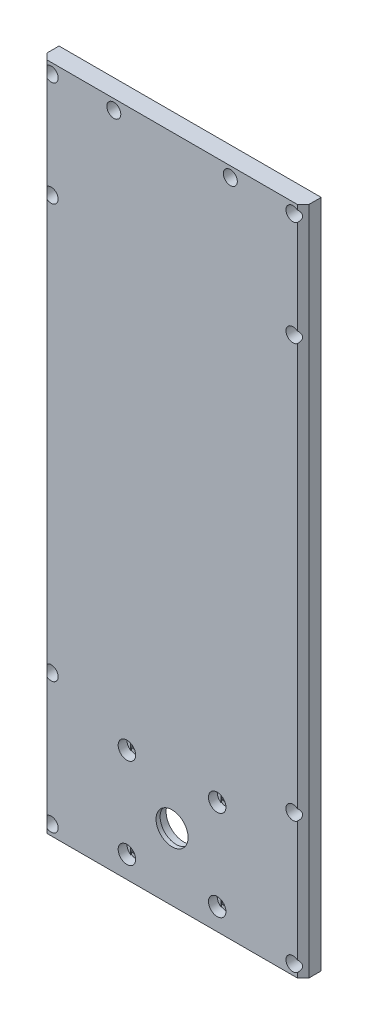
SolidWorks part; units mm, degrees
ref_plane "Front Plane" through (0, 0, 0) normal (0, 0, 1) x (1, 0, 0)
ref_plane "Top Plane" through (0, 0, 0) normal (0, 1, 0) x (1, 0, 0)
ref_plane "Right Plane" through (0, 0, 0) normal (1, 0, 0) x (0, 0, -1)
sketch "Sketch1" plane through (0, 0, 0) normal (0, 0, 1) x (1, 0, 0)
  line L1 (-45, -115) -> (45, -115)
  line L2 (-45, -115) -> (-45, 115)
  line L3 (-45, 115) -> (45, 115)
  line L4 (45, -115) -> (45, 115)
  line L5 (-45, -115) -> (45, 115) construction
  line L6 (-45, 115) -> (45, -115) construction
  line L7 (-38, -108) -> (38, -108)
  line L8 (-38, -108) -> (-38, 108)
  line L9 (-38, 108) -> (38, 108)
  line L10 (38, -108) -> (38, 108)
  line L11 (-38, -108) -> (38, 108) construction
  line L12 (-38, 108) -> (38, -108) construction
  point P0 (0, 0)
  point P6 (0, 0)
  dimension "D1" = 230
  dimension "D2" = 90
  dimension "D3" = 7
  dimension "D4" = 7
extrude "Boss-Extrude1" add sketch "Sketch1" along normal blind 7
sketch "Sketch2" plane through (0, 0, 7) normal (0, 0, 1) x (1, 0, 0)
  line L0 (38, -108) -> (38, 108) construction
  line L1 (-38, -108) -> (38, -108)
  line L2 (-38, -108) -> (-38, -72)
  line L3 (-38, -72) -> (38, -72)
  line L4 (38, -108) -> (38, -72)
  dimension "D1" = 36
extrude "Boss-Extrude2" add sketch "Sketch2" against normal up to surface (7 mm away) up to face at (0, 0, 0)
sketch "Sketch3" plane through (0, 0, 0) normal (0, 0, -1) x (-1, 0, 0)
  line L0 (0, -115) -> (0, -92) construction
  line L1 (45, -115) -> (-45, -115) construction
  circle A0 centre (0, -92) radius 5.5
  dimension "D1" = 11
  dimension "D2" = 23
extrude "Cut-Extrude1" cut sketch "Sketch3" against normal through all
sketch "Sketch4" plane through (0, 0, 0) normal (0, 0, -1) x (-1, 0, 0)
  circle A0 centre (0, -92) radius 6.05
  dimension "D1" = 12.1
extrude "Cut-Extrude2" cut sketch "Sketch4" against normal offset from surface (5.6 mm away) 1.4 up to face at (-5.5, -92, 7)
sketch "Sketch5" plane through (0, 0, 0) normal (0, 0, -1) x (-1, 0, 0)
  circle A0 centre (0, -92) radius 12
  dimension "D1" = 24
extrude "Cut-Extrude3" cut sketch "Sketch5" against normal offset from surface (3 mm away) 2.6 up to face at (-6.05, -92, 5.6)
sketch "Sketch6" plane through (0, 0, 0) normal (0, 0, -1) x (-1, 0, 0)
  line L1 (-15.5, -107.5) -> (15.5, -107.5) construction
  line L2 (-15.5, -107.5) -> (-15.5, -76.5) construction
  line L3 (-15.5, -76.5) -> (15.5, -76.5) construction
  line L4 (15.5, -107.5) -> (15.5, -76.5) construction
  line L5 (-15.5, -107.5) -> (15.5, -76.5) construction
  line L6 (-15.5, -76.5) -> (15.5, -107.5) construction
  circle A0 centre (-15.5, -76.5) radius 1.7
  circle A1 centre (15.5, -76.5) radius 1.7
  circle A2 centre (15.5, -107.5) radius 1.7
  circle A3 centre (-15.5, -107.5) radius 1.7
  point P0 (0, -92)
  dimension "D2" = 3.4
  dimension "D1" = 31
extrude "Cut-Extrude4" cut sketch "Sketch6" against normal through all
sketch "Sketch7" plane through (0, 0, 0) normal (0, 0, -1) x (-1, 0, 0)
  line L1 (-30, -112) -> (30, -112)
  line L2 (-30, -112) -> (-30, -72)
  line L3 (-30, -72) -> (30, -72)
  line L4 (30, -112) -> (30, -72)
  line L5 (-30, -112) -> (30, -72) construction
  line L6 (-30, -72) -> (30, -112) construction
  point P0 (0, -92)
  dimension "D1" = 60
  dimension "D2" = 40
extrude "Cut-Extrude5" cut sketch "Sketch7" against normal blind 1
sketch "Sketch8" plane through (0, 0, 7) normal (0, 0, 1) x (1, 0, 0)
  circle A0 centre (-15.5, -76.5) radius 3
  circle A1 centre (15.5, -76.5) radius 3
  circle A2 centre (15.5, -107.5) radius 3
  circle A3 centre (-15.5, -107.5) radius 3
  dimension "D1" = 6
extrude "Cut-Extrude6" cut sketch "Sketch8" against normal blind 3
sketch "Sketch9" plane through (0, 0, 7) normal (0, 0, 1) x (1, 0, 0)
  line L0 (-45, 115) -> (-45, -115) construction
  line L1 (-41.5, -111.5) -> (41.5, -111.5) construction
  line L2 (-41.5, -111.5) -> (-41.5, 111.5) construction
  line L3 (-41.5, 111.5) -> (41.5, 111.5) construction
  line L4 (41.5, -111.5) -> (41.5, 111.5) construction
  line L5 (-41.5, -111.5) -> (41.5, 111.5) construction
  line L6 (-41.5, 111.5) -> (41.5, -111.5) construction
  line L7 (45, 115) -> (-45, 115) construction
  circle A0 centre (-41.5, 111.5) radius 1.45
  circle A1 centre (41.5, 111.5) radius 1.45
  circle A4 centre (-41.5, -111.5) radius 1.45
  circle A5 centre (41.5, -111.5) radius 1.45
  circle A6 centre (-41.5, 75.5) radius 1.45
  circle A7 centre (41.5, 75.5) radius 1.45
  circle A8 centre (41.5, -66.5) radius 1.45
  circle A9 centre (-41.5, -66.5) radius 1.45
  point P0 (0, 0)
  dimension "D3" = 2.9
  dimension "D1" = 3.5
  dimension "D2" = 3.5
  dimension "D4" = 45
  dimension "D5" = 36
extrude "Cut-Extrude7" cut sketch "Sketch9" against normal through all
sketch "Sketch10" plane through (0, 0, 7) normal (0, 0, 1) x (1, 0, 0)
  circle A0 centre (-41.5, 111.5) radius 2.4
  circle A1 centre (41.5, 75.5) radius 2.4
  circle A2 centre (-41.5, 75.5) radius 2.4
  circle A3 centre (41.5, 111.5) radius 2.4
  circle A4 centre (-41.5, -111.5) radius 2.4
  circle A5 centre (41.5, -111.5) radius 2.4
  circle A6 centre (-41.5, -66.5) radius 2.4
  circle A7 centre (41.5, -66.5) radius 2.4
  dimension "D1" = 4.8
extrude "Cut-Extrude8" cut sketch "Sketch10" against normal blind 5
chamfer "Chamfer1" distance 2 angle 45 2 edges at (-45, 0, 7) (45, 0, 7)
sketch "Sketch11" plane through (0, 0, 7) normal (0, 0, 1) x (1, 0, 0)
  line L0 (38, -72) -> (38, 108) construction
  line L1 (-38, -72) -> (38, -72)
  line L2 (-38, -72) -> (-38, -36.4)
  line L3 (-38, -36.4) -> (38, -36.4)
  line L4 (38, -72) -> (38, -36.4)
  line L5 (-43, -115) -> (43, -115) construction
  dimension "D1" = 78.6
extrude "Boss-Extrude3" add sketch "Sketch11" against normal up to surface (7 mm away) up to face at (-40.05, -111.5, 0)
sketch "Sketch12" plane through (0, 0, 7) normal (0, 0, 1) x (1, 0, 0)
  line L0 (-41.5, 111.5) -> (41.5, 111.5) construction
  line L1 (-20, 111.5) -> (20, 111.5) construction
  circle A0 centre (-20, 111.5) radius 1.45
  circle A1 centre (20, 111.5) radius 1.45
  circle A2 centre (-41.5, 111.5) radius 1.45 construction
  point P7 (0, 111.5)
  dimension "D1" = 40
extrude "Cut-Extrude9" cut sketch "Sketch12" against normal through all
sketch "Sketch13" plane through (0, 0, 7) normal (0, 0, 1) x (1, 0, 0)
  circle A0 centre (-20, 111.5) radius 2.4
  circle A1 centre (20, 111.5) radius 2.4
  circle A2 centre (-41.5, 111.5) radius 2.4 construction
extrude "Cut-Extrude10" cut sketch "Sketch13" against normal up to surface (5 mm away) up to face at (-39.1, 111.5, 2)
chamfer "Chamfer2" distance 0.8 angle 45 12 edges at (0, -115, 0) (-45, 0, 0) (0, 115, 0) (45, 0, 0) (38, 35.8, 7) (0, 108, 7) (-38, 35.8, 7) (0, -36.4, 7) (-38, 35.8, 0) (0, 108, 0) (38, 35.8, 0) (0, -36.4, 0)
sketch "Sketch14" plane through (0, 0, 2) normal (0, 0, 1) x (1, 0, 0)
  line L2 (-42.95, -68.4125) -> (-42.95, -64.5875)
  line L4 (-40.05, -68.4125) -> (-40.05, -64.5875)
  line L5 (-42.95, -68.4125) -> (-40.05, -64.5875) construction
  line L6 (-42.95, -64.5875) -> (-40.05, -68.4125) construction
  line L14 (-42.95, -113.4125) -> (-42.95, -109.5875)
  line L16 (-40.05, -113.4125) -> (-40.05, -109.5875)
  line L17 (-42.95, -113.4125) -> (-40.05, -109.5875) construction
  line L18 (-42.95, -109.5875) -> (-40.05, -113.4125) construction
  line L26 (-42.95, 73.5875) -> (-42.95, 77.4125)
  line L28 (-40.05, 73.5875) -> (-40.05, 77.4125)
  line L29 (-42.95, 73.5875) -> (-40.05, 77.4125) construction
  line L30 (-42.95, 77.4125) -> (-40.05, 73.5875) construction
  line L32 (-21.45, 109.5875) -> (-21.45, 113.4125)
  line L34 (-18.55, 109.5875) -> (-18.55, 113.4125)
  line L35 (-21.45, 109.5875) -> (-18.55, 113.4125) construction
  line L36 (-21.45, 113.4125) -> (-18.55, 109.5875) construction
  line L38 (-42.95, 109.5875) -> (-42.95, 113.4125)
  line L40 (-40.05, 109.5875) -> (-40.05, 113.4125)
  line L41 (-42.95, 109.5875) -> (-40.05, 113.4125) construction
  line L42 (-42.95, 113.4125) -> (-40.05, 109.5875) construction
  arc A0 (-43, -68.3735) -> (-43, -64.6265) centre (-41.5, -66.5) ccw construction
  circle A2 centre (-41.5, -111.5) radius 2.4 construction
  circle A4 centre (-41.5, 75.5) radius 2.4 construction
  circle A5 centre (-20, 111.5) radius 2.4 construction
  circle A6 centre (-41.5, 111.5) radius 2.4 construction
  circle A7 centre (-41.5, 111.5) radius 1.45 construction
  circle A8 centre (-20, 111.5) radius 1.45 construction
  circle A9 centre (-41.5, 75.5) radius 1.45 construction
  circle A10 centre (-41.5, -66.5) radius 1.45 construction
  circle A12 centre (-41.5, -111.5) radius 1.45 construction
  arc A16 (-21.45, 109.5875) -> (-18.55, 109.5875) centre (-20, 111.5) ccw
  arc A17 (-40.05, 113.4125) -> (-42.95, 113.4125) centre (-41.5, 111.5) ccw
  arc A18 (-40.05, 77.4125) -> (-42.95, 77.4125) centre (-41.5, 75.5) ccw
  arc A20 (-42.95, -68.4125) -> (-40.05, -68.4125) centre (-41.5, -66.5) ccw
  arc A22 (-40.05, -109.5875) -> (-42.95, -109.5875) centre (-41.5, -111.5) ccw
  arc A23 (-42.95, 109.5875) -> (-40.05, 109.5875) centre (-41.5, 111.5) ccw
  arc A24 (-18.55, 113.4125) -> (-21.45, 113.4125) centre (-20, 111.5) ccw
  arc A25 (-42.95, 73.5875) -> (-40.05, 73.5875) centre (-41.5, 75.5) ccw
  arc A26 (-40.05, -64.5875) -> (-42.95, -64.5875) centre (-41.5, -66.5) ccw
  arc A29 (-42.95, -113.4125) -> (-40.05, -113.4125) centre (-41.5, -111.5) ccw
  point P0 (-41.5, -66.5)
  point P17 (-41.5, -111.5)
  point P33 (-41.5, 75.5)
  point P41 (-20, 111.5)
  point P49 (-41.5, 111.5)
extrude "Cut-Extrude11" cut sketch "Sketch14" against normal blind 0.2
sketch "Sketch15" plane through (0, 0, 1.8) normal (0, 0, 1) x (1, 0, 0)
  line L0 (-40.05, -111.5) -> (-40.05, -109.5875) construction
  line L1 (-42.95, -112.95) -> (-40.05, -112.95)
  line L2 (-42.95, -112.95) -> (-42.95, -110.05)
  line L3 (-42.95, -110.05) -> (-40.05, -110.05)
  line L4 (-40.05, -112.95) -> (-40.05, -110.05)
  line L5 (-42.95, -112.95) -> (-40.05, -110.05) construction
  line L6 (-42.95, -110.05) -> (-40.05, -112.95) construction
  line L7 (-40.05, 75.5) -> (-40.05, 77.4125) construction
  line L8 (-42.95, -67.95) -> (-40.05, -67.95)
  line L9 (-42.95, -67.95) -> (-42.95, -65.05)
  line L10 (-42.95, -65.05) -> (-40.05, -65.05)
  line L11 (-40.05, -67.95) -> (-40.05, -65.05)
  line L12 (-42.95, -67.95) -> (-40.05, -65.05) construction
  line L13 (-42.95, -65.05) -> (-40.05, -67.95) construction
  line L14 (-42.95, 74.05) -> (-40.05, 74.05)
  line L15 (-42.95, 74.05) -> (-42.95, 76.95)
  line L16 (-42.95, 76.95) -> (-40.05, 76.95)
  line L17 (-40.05, 74.05) -> (-40.05, 76.95)
  line L18 (-42.95, 74.05) -> (-40.05, 76.95) construction
  line L19 (-42.95, 76.95) -> (-40.05, 74.05) construction
  line L20 (-40.05, 109.5875) -> (-40.05, 113.4125) construction
  line L21 (-42.95, 110.05) -> (-40.05, 110.05)
  line L22 (-42.95, 110.05) -> (-42.95, 112.95)
  line L23 (-42.95, 112.95) -> (-40.05, 112.95)
  line L24 (-40.05, 110.05) -> (-40.05, 112.95)
  line L25 (-42.95, 110.05) -> (-40.05, 112.95) construction
  line L26 (-42.95, 112.95) -> (-40.05, 110.05) construction
  line L27 (-18.55, 109.5875) -> (-18.55, 113.4125) construction
  line L28 (-21.45, 110.05) -> (-18.55, 110.05)
  line L29 (-21.45, 110.05) -> (-21.45, 112.95)
  line L30 (-21.45, 112.95) -> (-18.55, 112.95)
  line L31 (-18.55, 110.05) -> (-18.55, 112.95)
  line L32 (-21.45, 110.05) -> (-18.55, 112.95) construction
  line L33 (-21.45, 112.95) -> (-18.55, 110.05) construction
  arc A0 (-40.05, -66.5) -> (-42.95, -66.5) centre (-41.5, -66.5) ccw construction
  arc A1 (-40.05, 75.5) -> (-42.95, 75.5) centre (-41.5, 75.5) ccw construction
  arc A2 (-18.55, 111.5) -> (-21.45, 111.5) centre (-20, 111.5) ccw construction
  arc A3 (-40.05, 111.5) -> (-42.95, 111.5) centre (-41.5, 111.5) ccw construction
  point P0 (-41.5, -111.5)
  point P8 (-41.5, -66.5)
  point P17 (-41.5, 75.5)
  point P28 (-41.5, 111.5)
  point P36 (-20, 111.5)
extrude "Cut-Extrude12" cut sketch "Sketch15" against normal blind 0.2
sketch "Sketch16" plane through (0, 0, 4) normal (0, 0, 1) x (1, 0, 0)
  line L2 (-17.2, -78.9718) -> (-17.2, -74.0282)
  line L4 (-13.8, -78.9718) -> (-13.8, -74.0282)
  line L5 (-17.2, -78.9718) -> (-13.8, -74.0282) construction
  line L6 (-17.2, -74.0282) -> (-13.8, -78.9718) construction
  line L8 (-17.2, -109.9718) -> (-17.2, -105.0282)
  line L10 (-13.8, -109.9718) -> (-13.8, -105.0282)
  line L11 (-17.2, -109.9718) -> (-13.8, -105.0282) construction
  line L12 (-17.2, -105.0282) -> (-13.8, -109.9718) construction
  circle A0 centre (-15.5, -76.5) radius 3 construction
  circle A1 centre (-15.5, -107.5) radius 3 construction
  circle A2 centre (-15.5, -107.5) radius 1.7 construction
  circle A3 centre (-15.5, -76.5) radius 1.7 construction
  circle A4 centre (-15.5, -107.5) radius 3 construction
  circle A5 centre (-15.5, -76.5) radius 3 construction
  arc A6 (-13.8, -105.0282) -> (-17.2, -105.0282) centre (-15.5, -107.5) ccw
  arc A7 (-17.2, -78.9718) -> (-13.8, -78.9718) centre (-15.5, -76.5) ccw
  arc A8 (-13.8, -74.0282) -> (-17.2, -74.0282) centre (-15.5, -76.5) ccw
  arc A9 (-17.2, -109.9718) -> (-13.8, -109.9718) centre (-15.5, -107.5) ccw
  point P0 (-15.5, -76.5)
  point P8 (-15.5, -107.5)
extrude "Cut-Extrude13" cut sketch "Sketch16" against normal blind 0.2
sketch "Sketch17" plane through (0, 0, 3.8) normal (0, 0, 1) x (1, 0, 0)
  line L0 (-13.8, -78.9718) -> (-13.8, -74.0282) construction
  line L1 (-17.2, -78.2) -> (-13.8, -78.2)
  line L2 (-17.2, -78.2) -> (-17.2, -74.8)
  line L3 (-17.2, -74.8) -> (-13.8, -74.8)
  line L4 (-13.8, -78.2) -> (-13.8, -74.8)
  line L5 (-17.2, -78.2) -> (-13.8, -74.8) construction
  line L6 (-17.2, -74.8) -> (-13.8, -78.2) construction
  line L7 (-13.8, -109.9718) -> (-13.8, -105.0282) construction
  line L8 (-17.2, -109.2) -> (-13.8, -109.2)
  line L9 (-17.2, -109.2) -> (-17.2, -105.8)
  line L10 (-17.2, -105.8) -> (-13.8, -105.8)
  line L11 (-13.8, -109.2) -> (-13.8, -105.8)
  line L12 (-17.2, -109.2) -> (-13.8, -105.8) construction
  line L13 (-17.2, -105.8) -> (-13.8, -109.2) construction
  arc A0 (-13.8, -107.5) -> (-17.2, -107.5) centre (-15.5, -107.5) ccw construction
  arc A1 (-13.8, -76.5) -> (-17.2, -76.5) centre (-15.5, -76.5) ccw construction
  point P0 (-15.5, -76.5)
  point P8 (-15.5, -107.5)
extrude "Cut-Extrude14" cut sketch "Sketch17" against normal blind 0.2
mirror "Mirror1" about plane through (0, 0, 0) normal (1, 0, 0) of "Cut-Extrude12", "Cut-Extrude13", "Cut-Extrude14", "Cut-Extrude11"
sketch "Sketch18" plane through (0, 0, 7) normal (0, 0, 1) x (1, 0, 0)
  line L0 (38.8, 108.8) -> (38.8, -37.2) construction
  line L1 (-38.8, 108.8) -> (38.8, 108.8)
  line L2 (-38.8, 108.8) -> (-38.8, 70.8)
  line L3 (-38.8, 70.8) -> (38.8, 70.8)
  line L4 (38.8, 108.8) -> (38.8, 70.8)
  dimension "D1" = 38
extrude "Boss-Extrude4" add sketch "Sketch18" against normal up to surface (7 mm away) up to face at (0, 35.8, 0)
chamfer "Chamfer3" distance 0.8 angle 45 1 edges at (0, 70.8, 7)
sketch "Sketch19" plane through (0, 0, 7) normal (0, 0, 1) x (1, 0, 0)
  line L1 (-38.8, 71.6) -> (38.8, 71.6)
  line L2 (-38.8, 71.6) -> (-38.8, -37.2)
  line L3 (-38.8, -37.2) -> (38.8, -37.2)
  line L4 (38.8, 71.6) -> (38.8, -37.2)
extrude "Boss-Extrude5" add sketch "Sketch19" against normal up to surface (7 mm away) up to face at (0, 16.8, 0)
